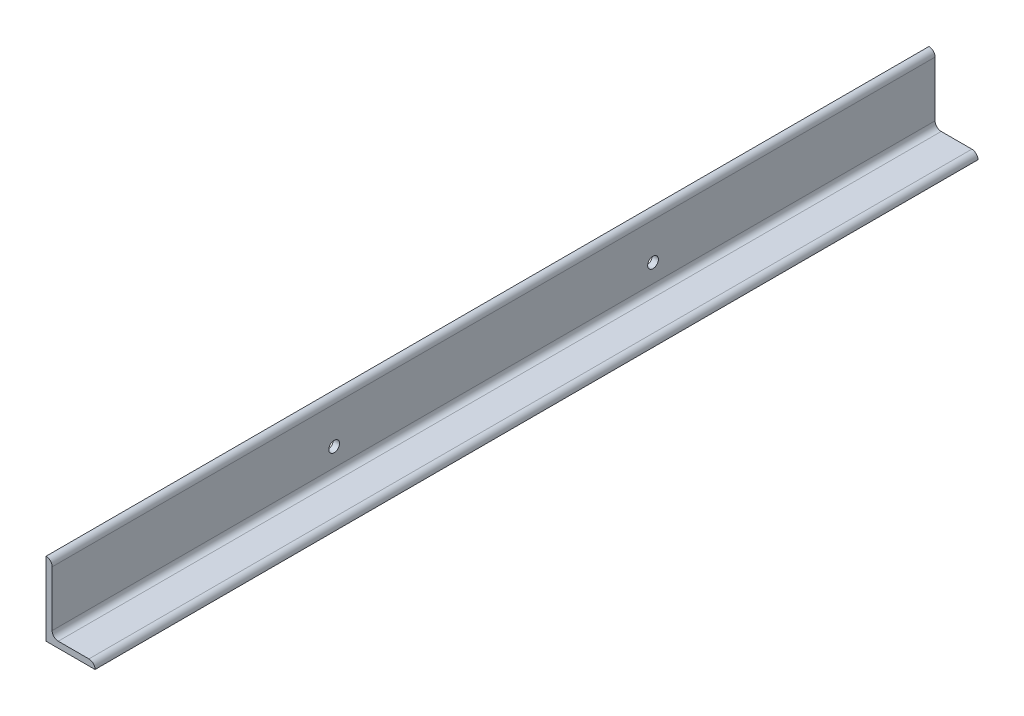
SolidWorks part; units mm, degrees
ref_plane "Front Plane" through (0, 0, 0) normal (0, 0, 1) x (1, 0, 0)
ref_plane "Top Plane" through (0, 0, 0) normal (0, 1, 0) x (1, 0, 0)
ref_plane "Right Plane" through (0, 0, 0) normal (1, 0, 0) x (0, 0, -1)
sketch "Sketch1" plane through (0, 0, 0) normal (0, 0, 1) x (1, 0, 0)
  line L0 (0, 0) -> (0, 152.4)
  line L1 (0, 152.4) -> (0.0051, 152.4)
  line L2 (12.7, 139.7051) -> (12.7, 25.4)
  line L3 (25.4, 12.7) -> (88.9051, 12.7)
  line L4 (101.6, 0.0051) -> (101.6, 0)
  line L5 (101.6, 0) -> (0, 0)
  arc A0 (101.6, 0.0051) -> (88.9051, 12.7) centre (88.9051, 0.0051) ccw
  arc A1 (0.0051, 152.4) -> (12.7, 139.7051) centre (0.0051, 139.7051) cw
  arc A2 (25.4, 12.7) -> (12.7, 25.4) centre (25.4, 25.4) cw
  circle A3 centre (0, 0) radius 12.7 construction
  dimension "D2" = 0.0051
  dimension "Radius_1" = 12.7
  dimension "Radius_2" = 12.7
  dimension "D1" = 12.7
  dimension "V_leg" = 152.4
  dimension "H_leg" = 101.6
  dimension "Thickness" = 12.7
  dimension "Flat_wid" = 0.0051
extrude "Boss-Extrude1" add sketch "Sketch1" along normal mid plane 1828.8
sketch "Sketch2" plane through (0, 0, 0) normal (-1, 0, 0) x (0, 0, 1)
  line L0 (914.4, 152.4) -> (914.4, 0) construction
  line L2 (914.4, 0) -> (-914.4, 0) construction
  circle A0 centre (330.2, 63.5) radius 11.1125
  circle A1 centre (-330.2, 63.5) radius 11.1125
  dimension "D1" = 22.225
  dimension "D3" = 660.4
  dimension "D4" = 63.5
  dimension "D5" = 63.5
  dimension "D2" = 584.2
extrude "Cut-Extrude1" cut sketch "Sketch2" against normal up to next
equation "\"D5@Sketch2\" = \"D4@Sketch2\""
